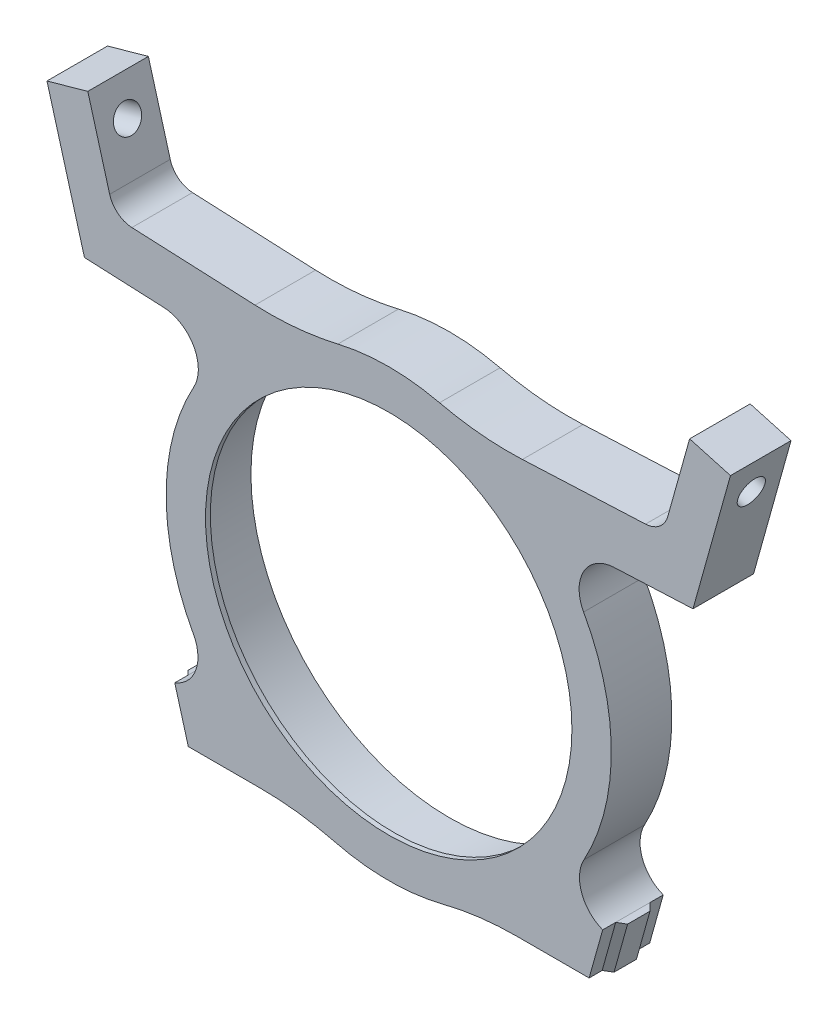
SolidWorks part; units mm, degrees
ref_plane "Ebene vorne" through (0, 0, 0) normal (0, 0, 1) x (1, 0, 0)
ref_plane "Ebene oben" through (0, 0, 0) normal (0, 1, 0) x (1, 0, 0)
ref_plane "Ebene rechts" through (0, 0, 0) normal (1, 0, 0) x (0, 0, -1)
sketch "Skizze1" plane through (0, 0, 0) normal (0, 0, 1) x (1, 0, 0)
  line L0 (-13.6359, -34.1266) -> (-33.0896, -34.1266)
  line L5 (-80.7379, 136.3891) -> (0, -152.5424) construction
  line L6 (-33.0896, -34.1266) -> (-35.3251, -26.1266)
  line L7 (-35.3251, -26.1266) -> (-25.845, -26.1266)
  line L8 (0, 0) -> (-26.219, 0) construction
  line L9 (0, 0) -> (0, -14.2745) construction
  line L10 (35.3251, -26.1266) -> (25.845, -26.1266)
  line L11 (33.0896, -34.1266) -> (35.3251, -26.1266)
  line L12 (13.6359, -34.1266) -> (33.0896, -34.1266)
  line L13 (-50.2356, 27.2324) -> (-25.845, 26.1266)
  line L14 (-13.6359, 34.1266) -> (-45.295, 35.562)
  line L15 (-50.2356, 27.2324) -> (-52.6564, 35.8957)
  line L16 (13.6359, 34.1266) -> (45.295, 35.562)
  line L17 (50.2356, 27.2324) -> (52.6564, 35.8957)
  line L18 (50.2356, 27.2324) -> (25.845, 26.1266)
  line L19 (80.7379, 136.3891) -> (0, -152.5424) construction
  line L20 (52.6564, 35.8957) -> (56.4242, 49.3792)
  line L21 (56.4242, 49.3792) -> (49.6825, 51.2631)
  line L22 (49.6825, 51.2631) -> (45.295, 35.562)
  line L23 (-52.6564, 35.8957) -> (-56.4242, 49.3792)
  line L24 (-56.4242, 49.3792) -> (-49.6825, 51.2631)
  line L25 (-49.6825, 51.2631) -> (-45.295, 35.562)
  circle A0 centre (0, 0) radius 32.75
  arc A1 (-13.6359, -34.1266) -> (13.6359, -34.1266) centre (0, 0) ccw
  arc A2 (-25.845, 26.1266) -> (-25.845, -26.1266) centre (0, 0) ccw
  arc A3 (25.845, -26.1266) -> (25.845, 26.1266) centre (0, 0) ccw
  arc A4 (13.6359, 34.1266) -> (-13.6359, 34.1266) centre (0, 0) ccw
  dimension "D1" = 65.5
  dimension "D2" = 4
  dimension "D3" = 8
  dimension "D4" = 14
  dimension "D5" = 7
extrude "Aufsatz-Linear austragen1" add sketch "Skizze1" along normal blind 10
sketch "Skizze2" plane through (0, 0, 10) normal (0, 0, 1) x (1, 0, 0)
  circle A0 centre (0, 0) radius 30.25
  circle A1 centre (0, 0) radius 32.75 construction
  circle A2 centre (0, 0) radius 32.75
  dimension "D1" = 2.5
extrude "Aufsatz-Linear austragen2" add sketch "Skizze2" against normal blind 0.8
sketch "Skizze5" plane through (32.7968, -9.1646, 0) normal (-0.9631, 0.2691, 0) x (0, 0, 1)
  line L0 (5, 62.7426) -> (5, 46.44) construction
  line L1 (10, 62.7426) -> (0, 62.7426) construction
  line L2 (10, 46.44) -> (0, 46.44) construction
  circle A0 centre (5, 56.9498) radius 2.25
  dimension "D1" = 4.5
extrude "Schnitt-Linear austragen1" cut sketch "Skizze5" against normal blind 10
mirror "Spiegeln1" about plane through (0, 0, 0) normal (1, 0, 0) of "Schnitt-Linear austragen1"
fillet "Verrundung1" radius 50 4 edges at (-13.6359, 34.1266, 5) (13.6359, 34.1266, 5) (-13.6359, -34.1266, 5) (13.6359, -34.1266, 5)
fillet "Verrundung2" radius 6 4 edges at (-25.845, -26.1266, 5) (25.845, -26.1266, 5) (25.845, 26.1266, 5) (-25.845, 26.1266, 5)
fillet "Verrundung3" radius 4 2 edges at (45.295, 35.562, 5) (-45.295, 35.562, 5)
ref_plane "Ebene1" through (6.4489, -23.0781, 0) normal (-0.2691, 0.9631, 0) x (0, 0, -1)
sketch "Skizze6" plane through (6.4489, -23.0781, 0) normal (-0.2691, 0.9631, 0) x (0, 0, -1)
  line L0 (-5, 41.0532) -> (-5, 46.0217) construction
  line L1 (-10, 41.0532) -> (0, 41.0532) construction
  line L2 (-7.85, 41.0532) -> (-6.85, 42.0532)
  line L3 (-6.85, 42.0532) -> (-3.15, 42.0532)
  line L4 (-2.15, 41.0532) -> (-3.15, 42.0532)
  line L5 (-2.15, 41.0532) -> (-7.85, 41.0532)
  point P9 (-5, 42.0532)
  dimension "D1" = 45
  dimension "D2" = 5.7
  dimension "D3" = 1
extrude "Aufsatz-Linear austragen3" add sketch "Skizze6" along normal up to vertex (8.3065 mm away) up to point (-35.3251, -26.1266, 10)
mirror "Spiegeln2" about plane through (0, 0, 0) normal (1, 0, 0) of "Aufsatz-Linear austragen3"
